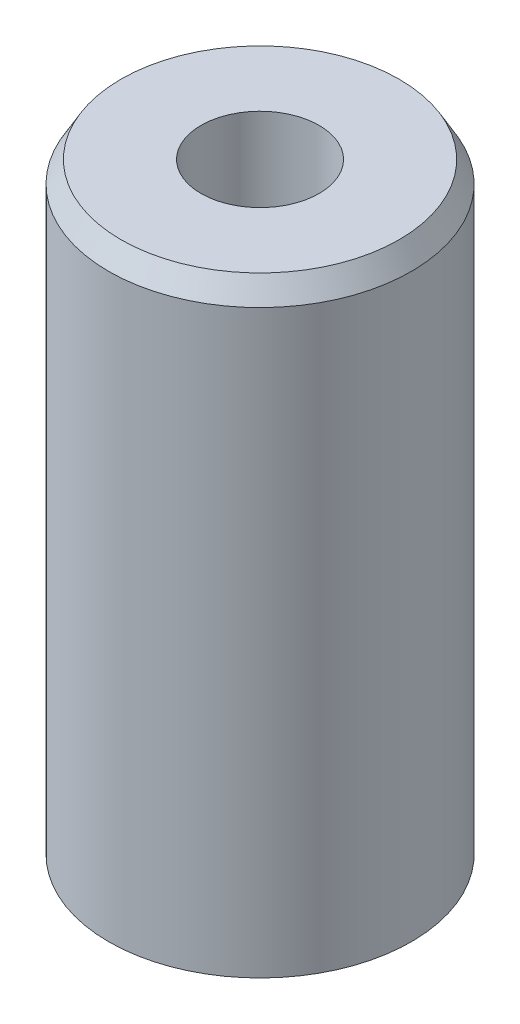
SolidWorks part; units mm, degrees
ref_plane "Front Plane" through (0, 0, 0) normal (0, 0, 1) x (1, 0, 0)
ref_plane "Top Plane" through (0, 0, 0) normal (0, 1, 0) x (1, 0, 0)
ref_plane "Right Plane" through (0, 0, 0) normal (1, 0, 0) x (0, 0, -1)
sketch "Sketch1" plane through (0, 0, 0) normal (0, 1, 0) x (1, 0, 0)
  circle A0 centre (0, 0) radius 25
  dimension "SHAFT_OD" = 50
extrude "Boss-Extrude1" add sketch "Sketch1" along normal blind 101.4402
sketch "Sketch2" plane through (0, 0, 0) normal (0, 1, 0) x (1, 0, 0)
  circle A0 centre (0, 0) radius 9.7556
  dimension "BORE_D" = 19.5111
extrude "Cut-Extrude1" cut sketch "Sketch2" along normal through all
chamfer "Chamfer1" distance 3.517 angle 30 2 edges at (0, 101.4402, 25) (0, 0, 25) first distance on face at (0, 101.4402, 25) first distance on face at (0, 0, 9.7556)
